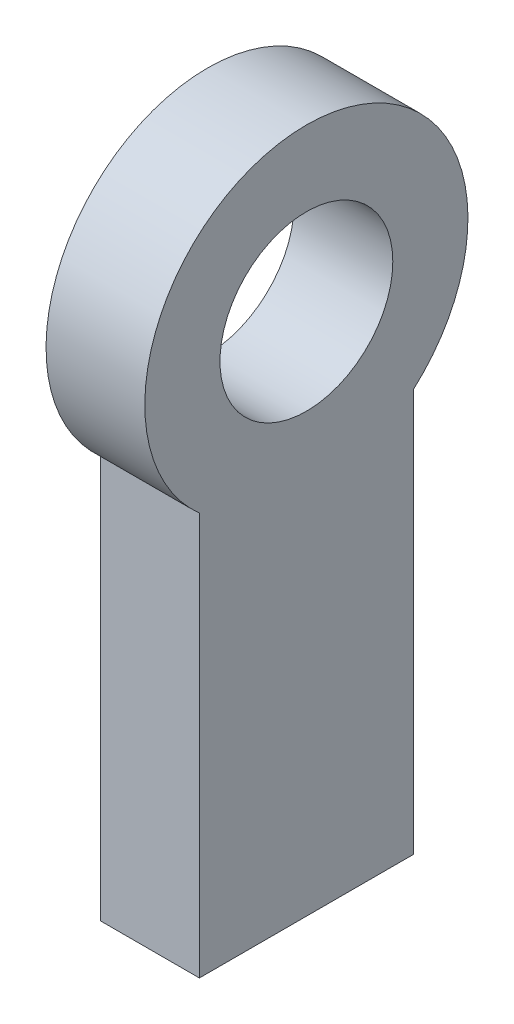
SolidWorks part; units mm, degrees
material "AISI 1020"
ref_plane "Спереди" through (0, 0, 0) normal (0, 0, 1) x (1, 0, 0)
ref_plane "Сверху" through (0, 0, 0) normal (0, 1, 0) x (1, 0, 0)
ref_plane "Справа" through (0, 0, 0) normal (1, 0, 0) x (0, 0, -1)
sketch "Эскиз1" plane through (0, 0, 0) normal (1, 0, 0) x (0, 0, -1)
  line L0 (-6.5, 16) -> (-6.5, -16) construction
  line L1 (0, 9.815) -> (-8.5, 4.9075) construction
  line L2 (-8.5, 4.9075) -> (-8.5, -4.9075) construction
  line L3 (-8.5, -4.9075) -> (0, -9.815) construction
  line L4 (0, -9.815) -> (8.5, -4.9075) construction
  line L5 (8.5, -4.9075) -> (8.5, 4.9075) construction
  line L6 (8.5, 4.9075) -> (0, 9.815) construction
  line L7 (-6.5, -31.815) -> (6.5, -31.815)
  line L8 (-6.5, -31.815) -> (-6.5, -7.3541)
  line L10 (6.5, -31.815) -> (6.5, -7.3541)
  line L11 (6.5, -16) -> (6.5, 16) construction
  line L12 (-6.5, -11.815) -> (6.5, -11.815) construction
  circle A0 centre (0, 0) radius 5.25
  circle A1 centre (0, 0) radius 8.5 construction
  arc A2 (6.5, -7.3541) -> (-6.5, -7.3541) centre (0, 0) ccw
  dimension "D1" = 10.5
  dimension "D2" = 17
  dimension "D3" = 2
  dimension "D4" = 20
base flange "Базовая кромка1" sketch "Эскиз1" thickness 6 reverse thickness direction yes parameters "D1"=0.74
sketch "Сгиб-Линии1" [suppressed] plane through (0, 0, 0) normal (0, 1, 0) x (1, 0, 0)
sketch "Граничная рамка1" [suppressed] plane through (0, 0, 0) normal (0, 1, 0) x (1, 0, 0)
sheet metal parameters "Листовой металл3" thickness 6 parameters "D1"=0.74
flat pattern "Развертка3" [suppressed]
sketch "Сгиб-Линии2" plane through (0, 0, 0) normal (0, 1, 0) x (1, 0, 0)
sketch3d "Граничная рамка2" [suppressed]
  line L0 (-9.8149, 9.8149, 0) -> (-9.8149, -31.815, 0) construction
  line L1 (9.8148, 9.8149, 0) -> (9.8148, -31.815, 0) construction
  line L2 (-9.8149, 9.8149, 0) -> (9.8148, 9.8149, 0) construction
  line L3 (-9.8149, -31.815, 0) -> (9.8148, -31.815, 0) construction
